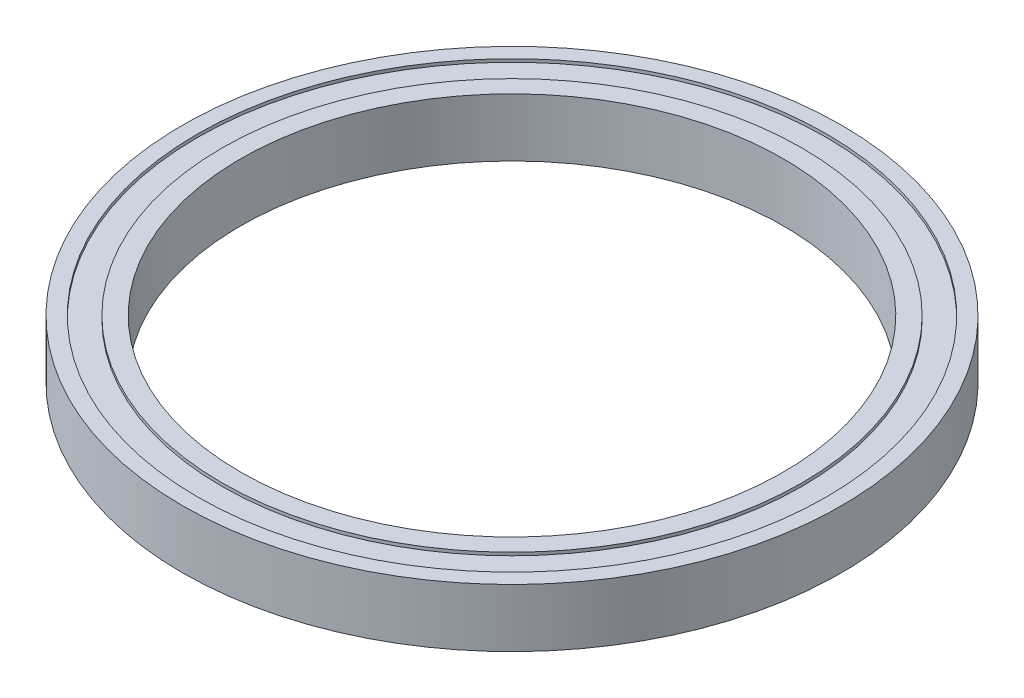
SolidWorks part; units mm, degrees
ref_plane "正面" through (0, 0, 0) normal (0, 0, 1) x (1, 0, 0)
ref_plane "平面" through (0, 0, 0) normal (0, 1, 0) x (1, 0, 0)
ref_plane "右側面" through (0, 0, 0) normal (1, 0, 0) x (0, 0, -1)
sketch "ｽｹｯﾁ1" plane through (0, 0, 0) normal (0, 1, 0) x (1, 0, 0)
  circle A0 centre (0, 0) radius 26.9875
  circle A1 centre (0, 0) radius 22.225
  dimension "D1" = 53.975
  dimension "D2" = 44.45
extrude "ﾎﾞｽ - 押し出し1" add sketch "ｽｹｯﾁ1" along normal blind 2.3815 and the other way blind 2.3815
sketch "ｽｹｯﾁ2" plane through (0, 2.3815, 0) normal (0, 1, 0) x (1, 0, 0)
  circle A0 centre (0, 0) radius 23.75
  circle A1 centre (0, 0) radius 25.75
  dimension "D1" = 51.5
  dimension "D2" = 47.5
extrude "ｶｯﾄ - 押し出し1" cut sketch "ｽｹｯﾁ2" against normal blind 0.254
mirror "ﾐﾗｰ1" about plane through (0, 0, 0) normal (0, 1, 0) of "ｶｯﾄ - 押し出し1"
